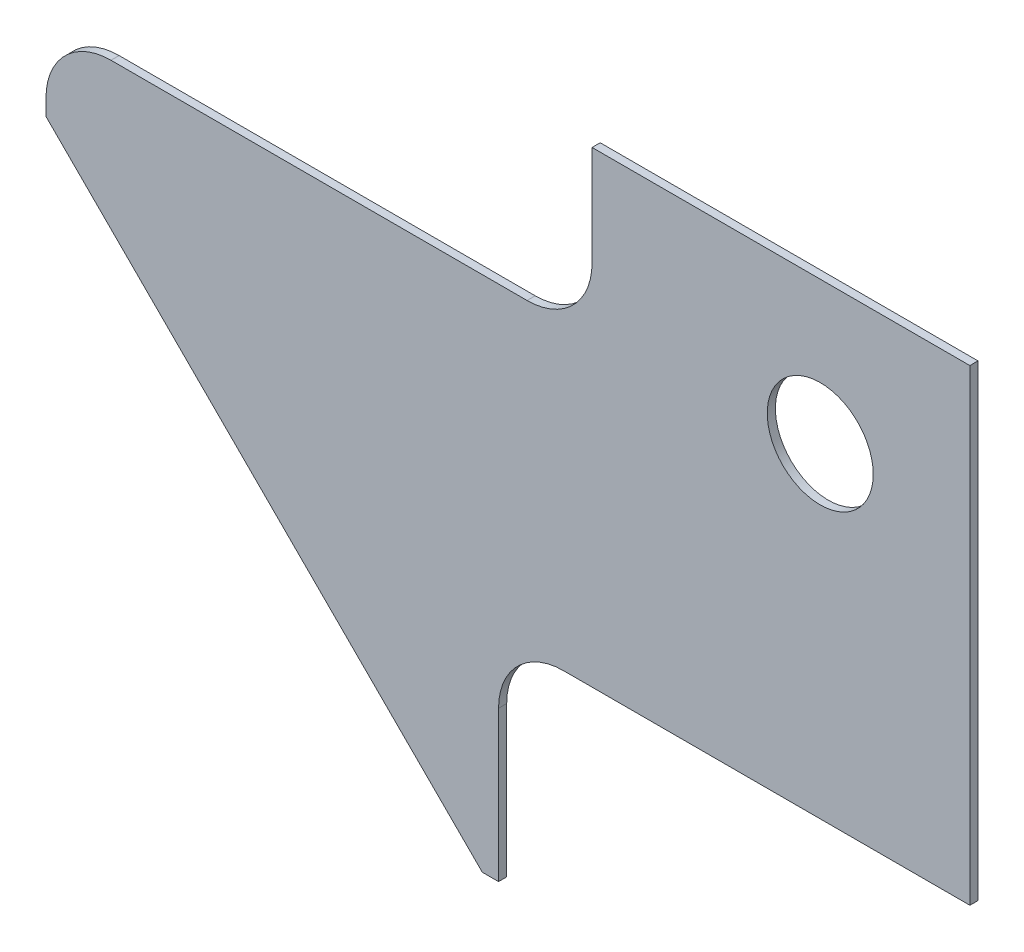
SolidWorks part; units mm, degrees
ref_plane "Front Plane" through (0, 0, 0) normal (0, 0, 1) x (1, 0, 0)
ref_plane "Top Plane" through (0, 0, 0) normal (0, 1, 0) x (1, 0, 0)
ref_plane "Right Plane" through (0, 0, 0) normal (1, 0, 0) x (0, 0, -1)
sketch "Sketch1" plane through (0, 0, 0) normal (0, 0, 1) x (1, 0, 0)
  line L0 (-138.2594, 48.9915) -> (32.2106, -121.4785)
  line L1 (32.2106, -121.4785) -> (222.7106, -121.4785)
  line L2 (-138.2594, 145.2215) -> (-138.2594, 48.9915)
  line L3 (-138.2594, 145.2215) -> (222.7106, 145.2215)
  line L4 (222.7106, -121.4785) -> (222.7106, 145.2215)
  circle A0 centre (164.2459, 89.532) radius 20.701
  circle A2 centre (164.2459, 89.532) radius 64.9605 construction
  circle A3 centre (164.2459, 89.532) radius 302.5053 construction
  point P0 (0, 0)
  point P2 (164.2459, 89.532)
  dimension "D4" = 211.0105
  dimension "D1" = 45
  dimension "D2" = 266.7
  dimension "D5" = 242.57
extrude "Boss-Extrude1" add sketch "Sketch1" along normal blind 3.175
sketch "Sketch2" plane through (0, 0, 3.175) normal (0, 0, 1) x (1, 0, 0)
  line L0 (32.2106, -121.4785) -> (222.7106, -121.4785) construction
  line L1 (222.7634, -121.4785) -> (38.5606, -121.4785)
  line L2 (222.7634, -121.4785) -> (222.7634, -37.4045)
  line L3 (222.7634, -37.4045) -> (38.5606, -37.4045)
  line L4 (38.5606, -121.4785) -> (38.5606, -37.4045)
extrude "Cut-Extrude1" cut sketch "Sketch2" against normal through all contours L3 L4 L1 L2
fillet "Fillet1" radius 25.4 1 edges at (38.5606, -37.4045, 1.5875)
sketch "Sketch4" plane through (0, 0, 3.175) normal (0, 0, 1) x (1, 0, 0)
  line L1 (-138.2594, 145.2215) -> (-138.2594, 48.9915) construction
  line L3 (-138.2594, 145.2215) -> (75.1006, 145.2215)
  line L4 (-138.2594, 145.2215) -> (-138.2594, 80.7415)
  line L5 (-138.2594, 80.7415) -> (75.1006, 80.7415)
  line L6 (75.1006, 145.2215) -> (75.1006, 80.7415)
extrude "Cut-Extrude2" cut sketch "Sketch4" against normal through all contours L5 L6 L3 L4
fillet "Fillet2" radius 25.4 2 edges at (-138.2594, 80.7415, 1.5875) (75.1006, 80.7415, 1.5875)
